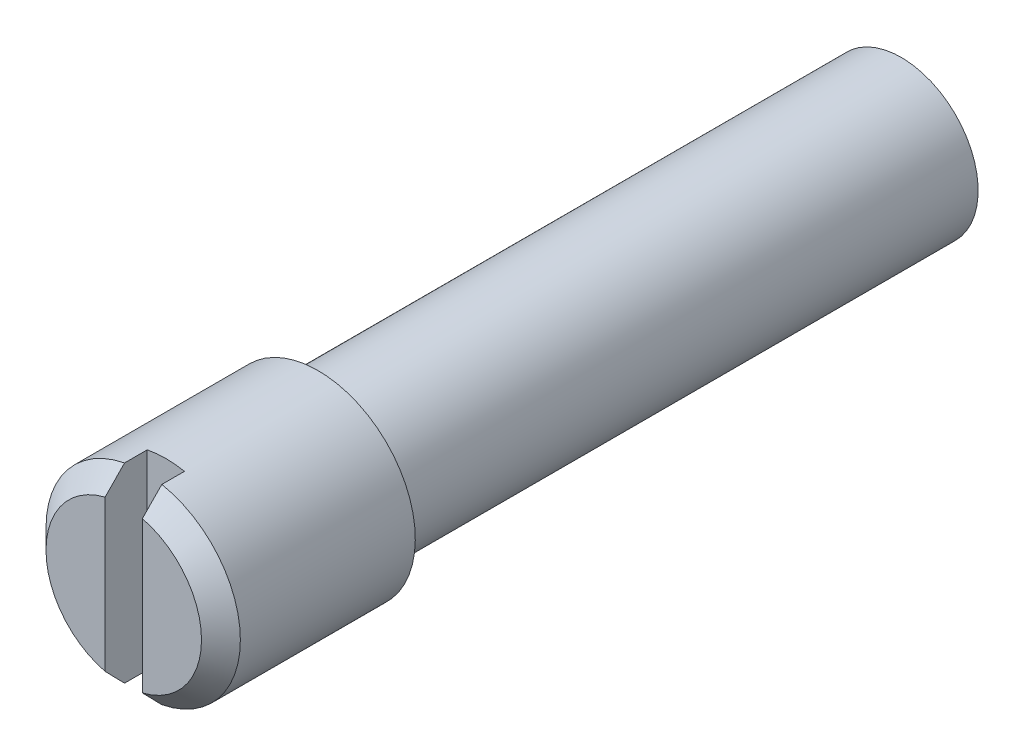
SolidWorks part; units mm, degrees
ref_plane "Plan1" through (0, 0, 0) normal (0, 0, 1) x (1, 0, 0)
ref_plane "Plan2" through (0, 0, 0) normal (0, 1, 0) x (1, 0, 0)
ref_plane "Plan3" through (0, 0, 0) normal (1, 0, 0) x (0, 0, -1)
ref_axis "Z Axis" through (0, 0, -50) along (0, 0, 1)
sketch "Esquisse1" plane through (0, 0, 0) normal (0, 1, 0) x (1, 0, 0)
  line L0 (0, 0) -> (0, 4) construction
  line L1 (0, 0) -> (3.5, 0)
  line L2 (0, 0) -> (0, 4)
  line L3 (0, 4) -> (3.1, 4)
  line L5 (3.5, 0) -> (3.5, 3.6)
  arc A0 (3.1, 4) -> (3.5, 3.6) centre (3.1, 3.6) cw
  dimension "D3" = 0.4
  dimension "D1" = 3.5
  dimension "D2" = 4
revolve "Base-Révolution" add sketch "Esquisse1" angle 360 about L0 reverse direction yes
sketch "Esquisse3" plane through (0, 0, 0) normal (0, 1, 0) x (1, 0, 0)
  line L1 (0, 0) -> (0, -24) construction
  line L2 (0, 0) -> (3, 0)
  line L3 (0, 0) -> (0, -24)
  line L4 (0, -24) -> (3, -24)
  line L6 (3, 0) -> (3, -24)
  dimension "D1" = 24
  dimension "D2" = 3
revolve "Boss.-Révol.1" add sketch "Esquisse3" angle 360 about L1 reverse direction yes
sketch "Esquisse4" plane through (0, 0, 0) normal (0, 1, 0) x (1, 0, 0)
  line L0 (2.573, -24.0427) -> (2.573, -23.9573)
  line L1 (-3, -24) -> (3, -24) construction
  line L2 (2.573, -23.9573) -> (3.0427, -23.6861)
  line L3 (2.573, -24.0427) -> (3.0427, -24.3139)
  line L4 (3.0427, -23.6861) -> (3.0427, -24.3139)
  line L5 (3, -24) -> (3, 0) construction
  point P4 (3, -24)
  dimension "D2" = 0.0427
  dimension "D3" = 0.0427
  dimension "D4" = 0.4697
  dimension "D5" = 60
  dimension "D1" = 0.427
  dimension "D6" = 60
chamfer "Chanfrein1" distance 0.6 angle 45 1 edges at (3, 0, 24)
sketch "Esquisse5" plane through (0, 0, 24) normal (0, 0, 1) x (1, 0, 0)
  circle A0 centre (0, 0) radius 3 construction
  circle A1 centre (0, 0) radius 3
curve "Hélice1" pitch 0.7 height 6 turns 8.5714
sweep "Enlèvement de matière-Balayage1" [suppressed] cut profiles "Esquisse4" path "Hélice1"
sketch "Esquisse6" plane through (0, 0, 0) normal (0, 0, 1) x (1, 0, 0)
  circle A0 centre (0, 0) radius 3.5 construction
  circle A1 centre (0, 0) radius 3.5
extrude "Enlèv. mat.-Extru.1" cut sketch "Esquisse6" against normal through all
sketch "Esquisse7" plane through (0, 0, 0) normal (0, 0, -1) x (-1, 0, 0)
  circle A0 centre (0, 0) radius 2.375
  dimension "D1" = 4.75
extrude "Enlèv. mat.-Extru.2" cut sketch "Esquisse7" against normal blind 18 flip side to cut
sketch "Esquisse8" plane through (0, 0, 24) normal (0, 0, 1) x (1, 0, 0)
  line L1 (0.575, 3.5843) -> (-0.575, 3.5843)
  line L2 (0.575, 3.5843) -> (0.575, -3.8664)
  line L3 (0.575, -3.8664) -> (-0.575, -3.8664)
  line L4 (-0.575, 3.5843) -> (-0.575, -3.8664)
  dimension "D1" = 1.15
  dimension "D2" = 0.575
extrude "Enlèv. mat.-Extru.3" cut sketch "Esquisse8" against normal blind 1.3
equation "\"D3@Esquisse1\"=\"D2@Esquisse1\"/10"
equation "\"D1@Chanfrein1\"=\"D2@Esquisse3\"*0.2"
equation "\"D3@Esquisse4\"=0.1*\"D1@Esquisse4\""
equation "\"D4@Esquisse4\"=1.1*\"D1@Esquisse4\""
equation "\"D2@Esquisse4\"=0.1*\"D1@Esquisse4\""
equation "\"D1@Esquisse4\"=0.61*\"D4@Hélice1\""
